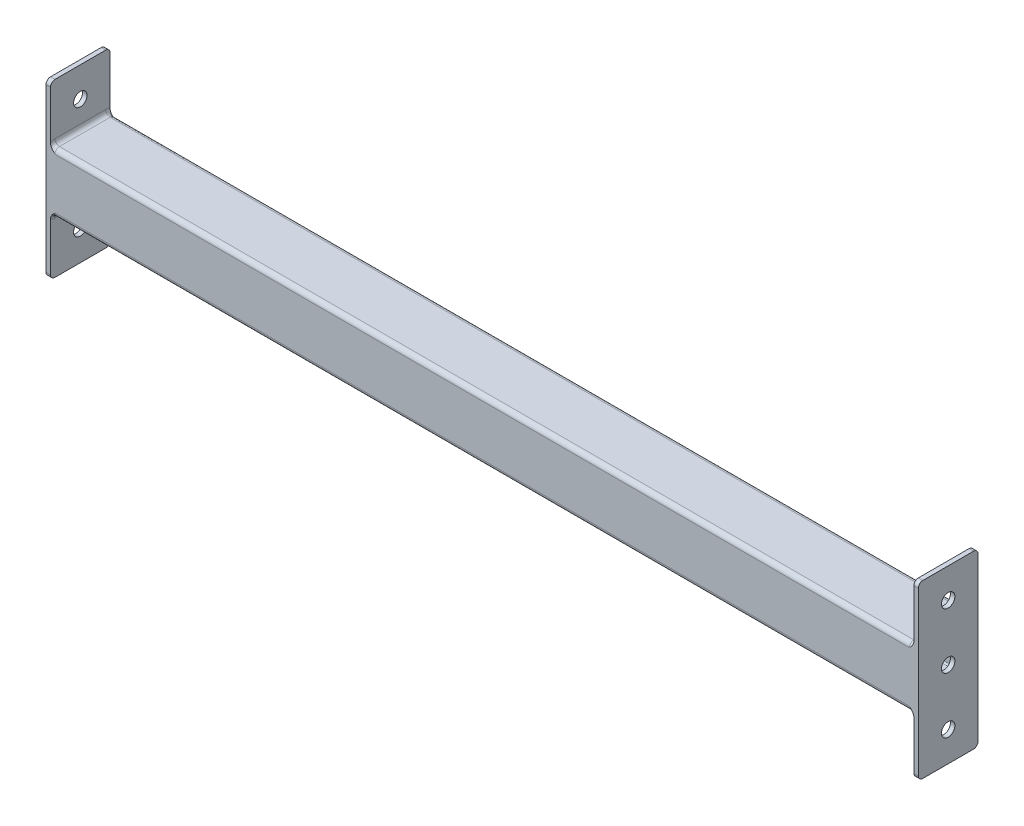
SolidWorks part; units mm, degrees
ref_plane "Front Plane" through (0, 0, 0) normal (0, 0, 1) x (1, 0, 0)
ref_plane "Top Plane" through (0, 0, 0) normal (0, 1, 0) x (1, 0, 0)
ref_plane "Right Plane" through (0, 0, 0) normal (1, 0, 0) x (0, 0, -1)
sketch "Sketch1" plane through (0, 0, 0) normal (1, 0, 0) x (0, 0, -1)
  line L1 (-20, -20) -> (20, -20)
  line L2 (-20, -20) -> (-20, 20)
  line L3 (-20, 20) -> (20, 20)
  line L4 (20, -20) -> (20, 20)
  line L5 (-20, -20) -> (20, 20) construction
  line L6 (-20, 20) -> (20, -20) construction
  line L7 (-17, -17) -> (17, -17)
  line L8 (-17, -17) -> (-17, 17)
  line L9 (-17, 17) -> (17, 17)
  line L10 (17, -17) -> (17, 17)
  line L11 (-17, -17) -> (17, 17) construction
  line L12 (-17, 17) -> (17, -17) construction
  point P0 (0, 0)
  point P6 (0, 0)
  dimension "D1" = 40
  dimension "D2" = 3
extrude "Boss-Extrude1" add sketch "Sketch1" along normal blind 289.5
fillet "Fillet1" radius 1 4 edges at (144.75, -17, -17) (144.75, 17, -17) (144.75, 17, 17) (144.75, -17, 17)
fillet "Fillet2" radius 3 4 edges at (144.75, -20, 20) (144.75, -20, -20) (144.75, 20, -20) (144.75, 20, 20)
sketch "Sketch2" plane through (289.5, 0, 0) normal (1, 0, 0) x (0, 0, -1)
  line L0 (0, -37.5) -> (0, 37.5) construction
  line L1 (-20, -57.5) -> (20, -57.5)
  line L2 (-20, -57.5) -> (-20, 57.5)
  line L3 (-20, 57.5) -> (20, 57.5)
  line L4 (20, -57.5) -> (20, 57.5)
  line L5 (-20, -57.5) -> (20, 57.5) construction
  line L6 (-20, 57.5) -> (20, -57.5) construction
  line L7 (-20, 57.5) -> (0, 37.5) construction
  line L8 (0, 37.5) -> (20, 57.5) construction
  circle A0 centre (0, 0) radius 4.5
  circle A1 centre (0, -37.5) radius 4.5
  circle A2 centre (0, 37.5) radius 4.5
  point P0 (0, 0)
  point P13 (0, 0)
  dimension "D3" = 9
  dimension "D1" = 40
  dimension "D2" = 75
extrude "Boss-Extrude2" add sketch "Sketch2" along normal blind 3
fillet "Fillet3" radius 3 6 edges at (289.5, -19.1213, 19.1213) (289.5, -20, 0) (289.5, 19.1213, -19.1213) (289.5, 19.1213, 19.1213) (289.5, -19.1213, -19.1213) (289.5, 20, 0)
fillet "Fillet4" radius 3 4 edges at (291, -57.5, -20) (291, -57.5, 20) (291, 57.5, 20) (291, 57.5, -20)
mirror "Mirror1" about plane through (0, 0, 0) normal (1, 0, 0) of bodies 102
